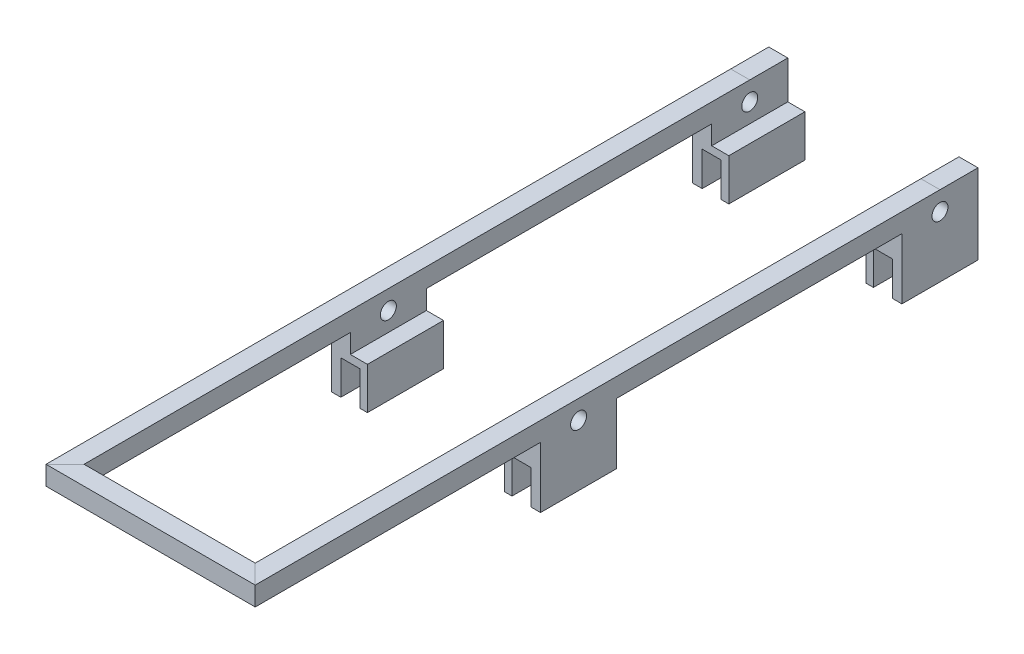
SolidWorks part; units mm, degrees
ref_plane "Front Plane" through (0, 0, 0) normal (0, 0, 1) x (1, 0, 0)
ref_plane "Top Plane" through (0, 0, 0) normal (0, 1, 0) x (1, 0, 0)
ref_plane "Right Plane" through (0, 0, 0) normal (1, 0, 0) x (0, 0, -1)
sketch "rail_path" plane through (0, 0, 0) normal (0, 1, 0) x (1, 0, 0)
  line L0 (28.575, 111.125) -> (28.575, 123.825)
  line L1 (-28.575, -111.125) -> (28.575, -111.125)
  line L2 (-28.575, -111.125) -> (-28.575, 111.125)
  line L3 (-28.575, 111.125) -> (28.575, 111.125) construction
  line L4 (28.575, -111.125) -> (28.575, 111.125)
  line L5 (-28.575, -111.125) -> (28.575, 111.125) construction
  line L6 (-28.575, 111.125) -> (28.575, -111.125) construction
  line L7 (-28.575, 111.125) -> (-28.575, 123.825)
  point P0 (0, 0)
  dimension "D1" = 222.25
  dimension "D2" = 57.15
  dimension "D3" = 12.7
  dimension "D4" = 12.7
sketch "rail_profile" plane through (0, 0, 0) normal (0, 0, 1) x (1, 0, 0)
  line L0 (-28.575, 0) -> (28.575, 0) construction
  line L1 (28.575, 0) -> (34.925, 0)
  line L2 (28.575, 0) -> (28.575, 6.35)
  line L3 (28.575, 6.35) -> (34.925, 6.35)
  line L4 (34.925, 0) -> (34.925, 6.35)
  line L5 (-28.575, 0) -> (28.575, 0) construction
  dimension "D1" = 6.35
  dimension "D2" = 6.35
sweep "Sweep1" add profiles "rail_profile" path "rail_path"
sketch "clip_profile" plane through (0, 0, 0) normal (0, 0, 1) x (1, 0, 0)
  line L2 (34.925, 0) -> (28.575, 0)
  line L4 (28.575, 0) -> (-28.575, 0)
  line L12 (-28.575, 6.35) -> (28.575, 6.35)
  line L16 (28.575, 0) -> (28.575, -6.35)
  line L18 (34.925, 0) -> (34.925, -6.35)
  line L19 (28.575, -6.35) -> (34.925, -6.35) construction
  line L30 (34.925, -6.35) -> (28.575, -6.35) construction
  line L31 (28.575, -6.35) -> (22.86, -6.35)
  line L33 (34.925, -6.35) -> (34.925, -20.32)
  line L34 (34.925, -20.32) -> (31.75, -20.32)
  line L35 (22.86, -6.35) -> (22.86, -20.32)
  line L37 (25.4, -20.32) -> (25.4, -8.89)
  line L38 (25.4, -8.89) -> (31.75, -8.89)
  line L39 (31.75, -20.32) -> (31.75, -8.89)
  line L40 (31.75, -20.32) -> (25.4, -20.32) construction
  line L41 (25.4, -20.32) -> (22.86, -20.32)
  line L42 (34.925, 6.35) -> (34.925, 0)
  line L43 (34.925, 0) -> (28.575, 0)
  line L45 (-28.575, 0) -> (-34.925, 0)
  line L46 (-34.925, 0) -> (-34.925, 6.35)
  line L47 (-34.925, 6.35) -> (-28.575, 6.35)
  line L49 (28.575, 6.35) -> (34.925, 6.35)
  dimension "D1" = 6.35
  dimension "D2" = 6.35
  dimension "D4" = 11.43
  dimension "D5" = 13.97
  dimension "D6" = 6.35
  dimension "D7" = 3.175
  dimension "D3" = 2.54
ref_plane "FrontClipPlane" through (0, 0, -111.125) normal (0, 0, -1) x (-1, 0, 0)
ref_plane "BackClipPlane" through (0, 0, 9.525) normal (0, 0, -1) x (-1, 0, 0)
sketch "BackClipProfile" plane through (0, 0, 9.525) normal (0, 0, -1) x (-1, 0, 0)
  line L0 (-34.925, 0) -> (-28.575, 0) construction
  line L1 (-28.575, -6.35) -> (-22.86, -6.35) construction
  line L2 (-22.86, -6.35) -> (-22.86, -20.32) construction
  line L3 (-25.4, -20.32) -> (-22.86, -20.32) construction
  line L4 (-25.4, -20.32) -> (-25.4, -8.89) construction
  line L5 (-25.4, -8.89) -> (-31.75, -8.89) construction
  line L6 (-31.75, -20.32) -> (-31.75, -8.89) construction
  line L7 (-34.925, -20.32) -> (-31.75, -20.32) construction
  line L8 (-34.925, -6.35) -> (-34.925, -20.32) construction
  line L10 (-28.575, 0) -> (-28.575, -6.35) construction
  line L11 (-34.925, 0) -> (-34.925, -6.35) construction
  line L12 (-34.925, 0) -> (-28.575, 0)
  line L13 (-28.575, -6.35) -> (-22.86, -6.35)
  line L14 (-22.86, -6.35) -> (-22.86, -20.32)
  line L15 (-25.4, -20.32) -> (-22.86, -20.32)
  line L16 (-25.4, -20.32) -> (-25.4, -8.89)
  line L17 (-25.4, -8.89) -> (-31.75, -8.89)
  line L18 (-31.75, -20.32) -> (-31.75, -8.89)
  line L19 (-34.925, -20.32) -> (-31.75, -20.32)
  line L20 (-34.925, -6.35) -> (-34.925, -20.32)
  line L22 (-28.575, 0) -> (-28.575, -6.35)
  line L23 (-34.925, 0) -> (-34.925, -6.35)
sketch "FrontClipProfile" plane through (0, 0, -111.125) normal (0, 0, -1) x (-1, 0, 0)
  line L0 (-34.925, -20.32) -> (-31.75, -20.32) construction
  line L1 (-31.75, -20.32) -> (-31.75, -8.89) construction
  line L2 (-25.4, -8.89) -> (-31.75, -8.89) construction
  line L3 (-25.4, -20.32) -> (-25.4, -8.89) construction
  line L4 (-25.4, -20.32) -> (-22.86, -20.32) construction
  line L5 (-22.86, -6.35) -> (-22.86, -20.32) construction
  line L6 (-28.575, -6.35) -> (-22.86, -6.35) construction
  line L8 (-34.925, -6.35) -> (-34.925, -20.32) construction
  line L9 (-28.575, 0) -> (-28.575, -6.35) construction
  line L10 (-34.925, 0) -> (-34.925, -6.35) construction
  line L11 (-34.925, 0) -> (-28.575, 0) construction
  line L12 (-34.925, -20.32) -> (-31.75, -20.32)
  line L13 (-31.75, -20.32) -> (-31.75, -8.89)
  line L14 (-25.4, -8.89) -> (-31.75, -8.89)
  line L15 (-25.4, -20.32) -> (-25.4, -8.89)
  line L16 (-25.4, -20.32) -> (-22.86, -20.32)
  line L17 (-22.86, -6.35) -> (-22.86, -20.32)
  line L18 (-28.575, -6.35) -> (-22.86, -6.35)
  line L20 (-34.925, -6.35) -> (-34.925, -20.32)
  line L21 (-28.575, 0) -> (-28.575, -6.35)
  line L22 (-34.925, 0) -> (-34.925, -6.35)
  line L23 (-34.925, 0) -> (-28.575, 0)
extrude "BackClip" add sketch "BackClipProfile" along normal mid plane 25.4
mirror "BackClipMirror" about plane through (0, 0, 0) normal (1, 0, 0) of "BackClip"
extrude "FrontClip" add sketch "FrontClipProfile" along normal mid plane 25.4
mirror "FrontClipMirror" about plane through (0, 0, 0) normal (1, 0, 0) of "FrontClip"
sketch "Sketch8" plane through (28.575, 0, 0) normal (-1, 0, 0) x (0, 0, 1)
  line L0 (-123.825, 6.35) -> (-123.825, -6.35) construction
  line L1 (-123.825, -6.35) -> (-98.425, -6.35) construction
  line L2 (-98.425, -6.35) -> (-98.425, 0) construction
  line L9 (111.125, 6.35) -> (-111.125, 6.35) construction
  line L12 (-111.125, 6.35) -> (-123.825, 6.35) construction
  line L13 (-98.425, -6.35) -> (-98.425, 0) construction
  line L14 (-123.825, -6.35) -> (-98.425, -6.35) construction
  line L15 (-111.125, 6.35) -> (-123.825, 6.35) construction
  line L16 (-123.825, 6.35) -> (-123.825, -6.35) construction
  line L17 (111.125, 6.35) -> (-111.125, 6.35) construction
  line L18 (-123.825, 6.35) -> (-98.425, -6.35) construction
  line L19 (22.225, -6.35) -> (22.225, 0) construction
  line L20 (-3.175, -6.35) -> (22.225, -6.35) construction
  line L21 (-3.175, -6.35) -> (-3.175, 0) construction
  line L22 (22.225, -6.35) -> (22.225, 0) construction
  line L23 (-3.175, -6.35) -> (22.225, -6.35) construction
  line L24 (-3.175, -6.35) -> (-3.175, 0) construction
  line L25 (-3.175, -6.35) -> (22.225, 6.35) construction
  circle A0 centre (-111.125, 0) radius 2.667
  circle A1 centre (9.525, 0) radius 2.667
  dimension "D1" = 5.334
  dimension "D2" = 5.334
extrude "Cut-Extrude1" cut sketch "Sketch8" against normal through all both and the other way through all
equation "\"rail_horizontal_clearance\"= 0.25 / 2"
